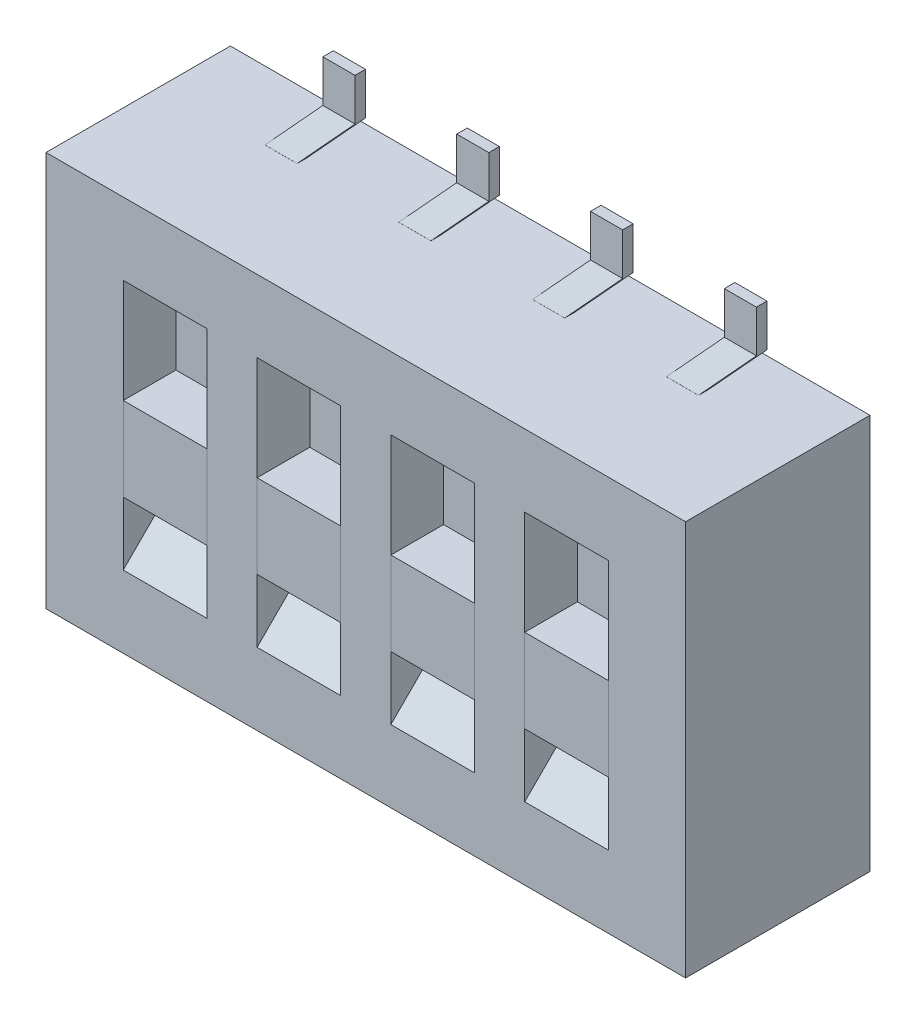
SolidWorks part; units mm, degrees
ref_plane "Спереди" through (0, 0, 0) normal (0, 0, 1) x (1, 0, 0)
ref_plane "Сверху" through (0, 0, 0) normal (0, 1, 0) x (1, 0, 0)
ref_plane "Справа" through (0, 0, 0) normal (1, 0, 0) x (0, 0, -1)
sketch "Эскиз1" plane through (0, 0, 0) normal (0, 0, 1) x (1, 0, 0)
  line L1 (-6.07, -3.75) -> (6.07, -3.75)
  line L2 (-6.07, -3.75) -> (-6.07, 3.75)
  line L3 (-6.07, 3.75) -> (6.07, 3.75)
  line L4 (6.07, -3.75) -> (6.07, 3.75)
  line L5 (-6.07, -3.75) -> (6.07, 3.75) construction
  line L6 (-6.07, 3.75) -> (6.07, -3.75) construction
  point P0 (0, 0)
  dimension "D1" = 12.14
  dimension "D2" = 7.5
extrude "Бобышка-Вытянуть1" add sketch "Эскиз1" along normal blind 3.5
sketch "Эскиз2" plane through (0, 0, 3.5) normal (0, 0, 1) x (1, 0, 0)
  line L0 (1.925, 0) -> (-1.925, 0) construction
  line L1 (-4.6037, -1.3813) -> (-3.0162, -1.3813)
  line L2 (-4.6037, -1.3813) -> (-4.6037, 1.3813)
  line L3 (-4.6037, 1.3813) -> (-3.0162, 1.3813)
  line L4 (-3.0162, -1.3813) -> (-3.0162, 1.3813)
  line L5 (-4.6037, -1.3813) -> (-3.0162, 1.3813) construction
  line L6 (-4.6037, 1.3813) -> (-3.0162, -1.3813) construction
  line L7 (-6.07, 3.75) -> (-6.07, -3.75) construction
  point P0 (-3.81, 0)
  point P5 (0, 0)
  point P8 (0, 0)
  point P9 (0, 0)
  dimension "D1" = 1.5875
  dimension "D2" = 2.7625
  dimension "D3" = 2.26
extrude "Вырез-Вытянуть1" cut sketch "Эскиз2" against normal blind 1
chamfer "Фаска1" distance 1 angle 45 2 edges at (-3.81, 1.3813, 3.5) (-3.81, -1.3813, 3.5)
sketch "Эскиз3" plane through (0, 0, 2.5) normal (0, 0, 1) x (1, 0, 0)
  line L0 (-4.6037, 1.3813) -> (-4.6037, -1.3813) construction
  line L1 (-4.6037, -1.1812) -> (-3.0163, -1.1812)
  line L2 (-4.6037, -1.1812) -> (-4.6037, 0.4062)
  line L3 (-4.6037, 0.4062) -> (-3.0163, 0.4062)
  line L4 (-3.0163, -1.1812) -> (-3.0163, 0.4062)
  line L5 (-3.0162, -1.3813) -> (-3.0162, 1.3813) construction
  line L6 (-4.6037, -1.3813) -> (-3.0162, -1.3813) construction
  point P10 (-3.81, -1.3813)
  dimension "D1" = 0.2
extrude "Бобышка-Вытянуть3" add sketch "Эскиз3" along normal blind 1 separate body
pattern_linear "Линейный массив1" count 4 spacing 2.54 along (1, 0, 0) of "Вырез-Вытянуть1", "Фаска1"
pattern_linear "Линейный массив2" count 4 spacing 2.54 along (1, 0, 0) of "Бобышка-Вытянуть3"
sketch "Эскиз4" plane through (0, 0, 0) normal (0, 0, 1) x (1, 0, 0)
  line L0 (-6.07, 3.75) -> (-6.07, -3.75) construction
  line L5 (-4.115, -3.85) -> (-3.505, -3.85)
  line L6 (-4.115, -3.85) -> (-4.115, -4.65)
  line L7 (-4.115, -4.65) -> (-3.505, -4.65)
  line L8 (-3.505, -3.85) -> (-3.505, -4.65)
  line L9 (-4.115, -3.85) -> (-3.505, -4.65) construction
  line L10 (-4.115, -4.65) -> (-3.505, -3.85) construction
  point P0 (-3.81, -4.25)
  point P9 (0, 0)
  dimension "D1" = 2.26
  dimension "D2" = 0.61
  dimension "D3" = 0.8
  dimension "D4" = 4.65
extrude "Бобышка-Вытянуть4" add sketch "Эскиз4" along normal blind 0.2 separate body
sketch "Эскиз5" plane through (0, -3.75, 0) normal (0, -1, 0) x (1, 0, 0)
  line L0 (-4.115, 0) -> (-3.505, 0) construction
  line L1 (-4.115, 1.1) -> (-3.505, 1.1)
  line L2 (-4.115, 1.1) -> (-4.115, 1.3)
  line L3 (-4.115, 1.3) -> (-3.505, 1.3)
  line L4 (-3.505, 1.1) -> (-3.505, 1.3)
  line L5 (-4.115, 1.1) -> (-3.505, 1.3) construction
  line L6 (-4.115, 1.3) -> (-3.505, 1.1) construction
  line L7 (-6.07, 0) -> (6.07, 0) construction
  point P0 (-3.81, 1.2)
  point P5 (0, 0)
  dimension "D1" = 1.2
  dimension "D2" = 0.2
extrude "Бобышка-Вытянуть5" add sketch "Эскиз5" along normal blind 0.001 separate body
loft "По сечениям1" add section face at (-3.81, -3.751, 1.2) section face at (-3.81, -3.85, 0.1) connector at (-3.505, -3.751, 1.1) connector at (-3.505, -3.85, 0)
pattern_linear "Линейный массив3" count 4 spacing 2.54 along (1, 0, 0) of bodies 111
mirror "Зеркальное отражение4" about plane through (0, 0, 0) normal (0, 1, 0) of bodies 112 113 114 111
